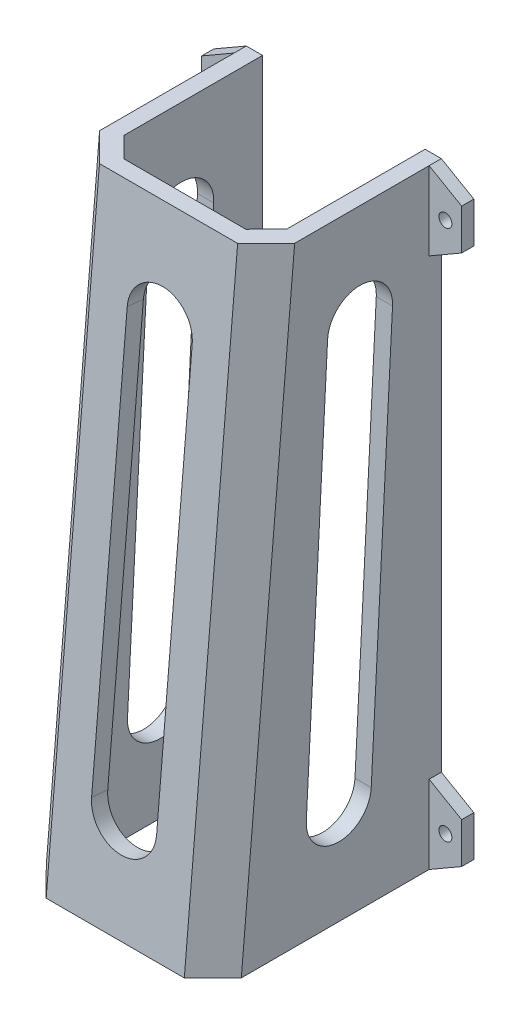
SolidWorks part; units mm, degrees
ref_plane "前视基准面" through (0, 0, 0) normal (0, 0, 1) x (1, 0, 0)
ref_plane "上视基准面" through (0, 0, 0) normal (0, 1, 0) x (1, 0, 0)
ref_plane "右视基准面" through (0, 0, 0) normal (1, 0, 0) x (0, 0, -1)
ref_plane "Plane1" through (0, 3.1365, 35.8502) normal (0, 0.0872, 0.9962) x (1, 0, 0)
sketch "Sketch2" plane through (0, 0, 0) normal (0, 0, 1) x (1, 0, 0)
  line L0 (0, 0) -> (0, -32.0686) construction
  line L1 (20, -80) -> (20, -230)
  line L2 (-24, -80) -> (-20, -80)
  line L3 (-24, -80) -> (-24, -230)
  line L4 (-24, -230) -> (-20, -230)
  line L5 (-20, -80) -> (-20, -230)
  line L6 (24, -230) -> (20, -230)
  line L7 (24, -80) -> (24, -230)
  line L8 (24, -80) -> (20, -80)
  dimension "D1" = 4
  dimension "D2" = 20
  dimension "D3" = 150
  dimension "D4" = 80
extrude "Boss-Extrude1" add sketch "Sketch2" along normal up to surface (43.1237 mm away) up to plane "Plane1"
sketch "Sketch3" plane through (0, 3.1365, 35.8502) normal (0, 0.0872, 0.9962) x (1, 0, 0)
  line L1 (24, -83.4541) -> (-24, -83.4541)
  line L2 (24, -83.4541) -> (24, -234.027)
  line L3 (24, -234.027) -> (-24, -234.027)
  line L4 (-24, -83.4541) -> (-24, -234.027)
extrude "Boss-Extrude2" add sketch "Sketch3" against normal blind 4
sketch "Sketch4" plane through (0, -230, 0) normal (0, -1, 0) x (1, 0, 0)
  line L1 (-43.9644, 72.2467) -> (43.9915, 72.2467)
  line L2 (-43.9644, 72.2467) -> (-43.9644, 31.0078)
  line L3 (-43.9644, 31.0078) -> (43.9915, 31.0078)
  line L4 (43.9915, 72.2467) -> (43.9915, 31.0078)
extrude "Cut-Extrude1" cut sketch "Sketch4" along normal blind 10
chamfer "Chamfer1" distance 5 angle 45 2 edges at (20, -155.1743, 45.6854) (-20, -155.1743, 45.6854)
chamfer "Chamfer2" distance 7 angle 45 2 edges at (24, -155, 49.6854) (-24, -155, 49.6854)
sketch "Sketch5" plane through (-24, 0, 0) normal (-1, 0, 0) x (0, 0, 1)
  line L0 (20, -105) -> (25.2408, -205) construction
  line L1 (27.989, -104.5813) -> (33.2298, -204.5813)
  line L2 (12.011, -105.4187) -> (17.2517, -205.4187)
  line L3 (0, -80) -> (0, -230) construction
  line L4 (36.097, -80) -> (0, -80) construction
  line L5 (49.2203, -230) -> (0, -230) construction
  arc A0 (27.989, -104.5813) -> (12.011, -105.4187) centre (20, -105) ccw
  arc A1 (17.2517, -205.4187) -> (33.2298, -204.5813) centre (25.2408, -205) ccw
  point P2 (22.6204, -155)
  dimension "D5" = 8
  dimension "D1" = 3
  dimension "D2" = 25
  dimension "D3" = 25
  dimension "D4" = 20
extrude "Cut-Extrude2" cut sketch "Sketch5" against normal blind 100
sketch "Sketch6" plane through (0, -83.1365, 7.2735) normal (0, 0.9962, -0.0872) x (1, 0, 0)
  line L8 (-17, -35.9872) -> (17, -35.9872)
  line L9 (17, -35.9872) -> (20, -32.9872)
  line L10 (20, -32.9872) -> (20, -26.9872)
  line L11 (20, -32.9872) -> (20, -26.9872)
  line L12 (15, -31.9872) -> (-15, -31.9872)
  line L13 (20, -26.9872) -> (15, -31.9872)
  line L14 (20, -26.9872) -> (15, -31.9872)
  line L15 (-20, -32.9872) -> (-17, -35.9872)
  line L16 (-17, -35.9872) -> (17, -35.9872)
  line L17 (17, -35.9872) -> (20, -32.9872)
  line L20 (15, -31.9872) -> (-15, -31.9872)
  line L23 (-20, -32.9872) -> (-17, -35.9872)
  line L24 (-15, -31.9872) -> (-20, -26.9872)
  line L25 (-15, -31.9872) -> (-20, -26.9872)
  line L26 (-20, -26.9872) -> (-20, -32.9872)
  line L27 (-20, -26.9872) -> (-20, -32.9872)
  dimension "D1" = 0
extrude "Boss-Extrude3" add sketch "Sketch6" along normal up to surface (0.7874 mm away) up to face at (22, -80, 19.0523)
sketch "Sketch7" plane through (0, 0, 0) normal (0, 0, -1) x (-1, 0, 0)
  line L0 (0, -80) -> (0, -230) construction
  line L1 (15, -80) -> (-15, -80) construction
  line L2 (-15, -230) -> (15, -230) construction
  line L3 (-24, -155) -> (24, -155) construction
  line L4 (-24, -230) -> (-24, -80) construction
  line L5 (24, -80) -> (24, -230) construction
  line L6 (-24, -80) -> (-32, -84.6188)
  line L7 (-32, -84.6188) -> (-32, -94.6188)
  line L8 (-32, -94.6188) -> (-24, -99.2376)
  line L9 (-24, -99.2376) -> (-24, -80)
  line L10 (-24, -210.7624) -> (-24, -230)
  line L11 (-32, -215.3812) -> (-24, -210.7624)
  line L12 (-32, -225.3812) -> (-32, -215.3812)
  line L13 (-24, -230) -> (-32, -225.3812)
  line L14 (24, -230) -> (32, -225.3812)
  line L15 (32, -225.3812) -> (32, -215.3812)
  line L16 (32, -215.3812) -> (24, -210.7624)
  line L17 (24, -210.7624) -> (24, -230)
  line L18 (24, -99.2376) -> (24, -80)
  line L19 (32, -94.6188) -> (24, -99.2376)
  line L20 (32, -84.6188) -> (32, -94.6188)
  line L21 (24, -80) -> (32, -84.6188)
  circle A0 centre (-28, -89.6188) radius 1.6
  circle A1 centre (-28, -220.3812) radius 1.6
  circle A2 centre (28, -220.3812) radius 1.6
  circle A3 centre (28, -89.6188) radius 1.6
  dimension "D4" = 3.2
  dimension "D5" = 4
  dimension "D6" = 5
  dimension "D1" = 60
  dimension "D2" = 8
  dimension "D3" = 10
extrude "Boss-Extrude4" add sketch "Sketch7" against normal blind 3
sketch "Sketch8" plane through (0, 3.1365, 35.8502) normal (0, 0.0872, 0.9962) x (1, 0, 0)
  line L0 (0, -108.4541) -> (0, -209.027) construction
  line L1 (8, -108.4541) -> (8, -209.027)
  line L2 (-8, -108.4541) -> (-8, -209.027)
  line L3 (17, -83.4541) -> (-17, -83.4541) construction
  line L4 (-17, -234.027) -> (17, -234.027) construction
  line L7 (0, -108.4541) -> (0, -83.4541) construction
  arc A0 (8, -108.4541) -> (-8, -108.4541) centre (0, -108.4541) ccw
  arc A1 (-8, -209.027) -> (8, -209.027) centre (0, -209.027) ccw
  point P2 (0, -158.7405)
  dimension "D1" = 8
  dimension "D2" = 25
  dimension "D3" = 25
extrude "Cut-Extrude3" cut sketch "Sketch8" against normal blind 13
